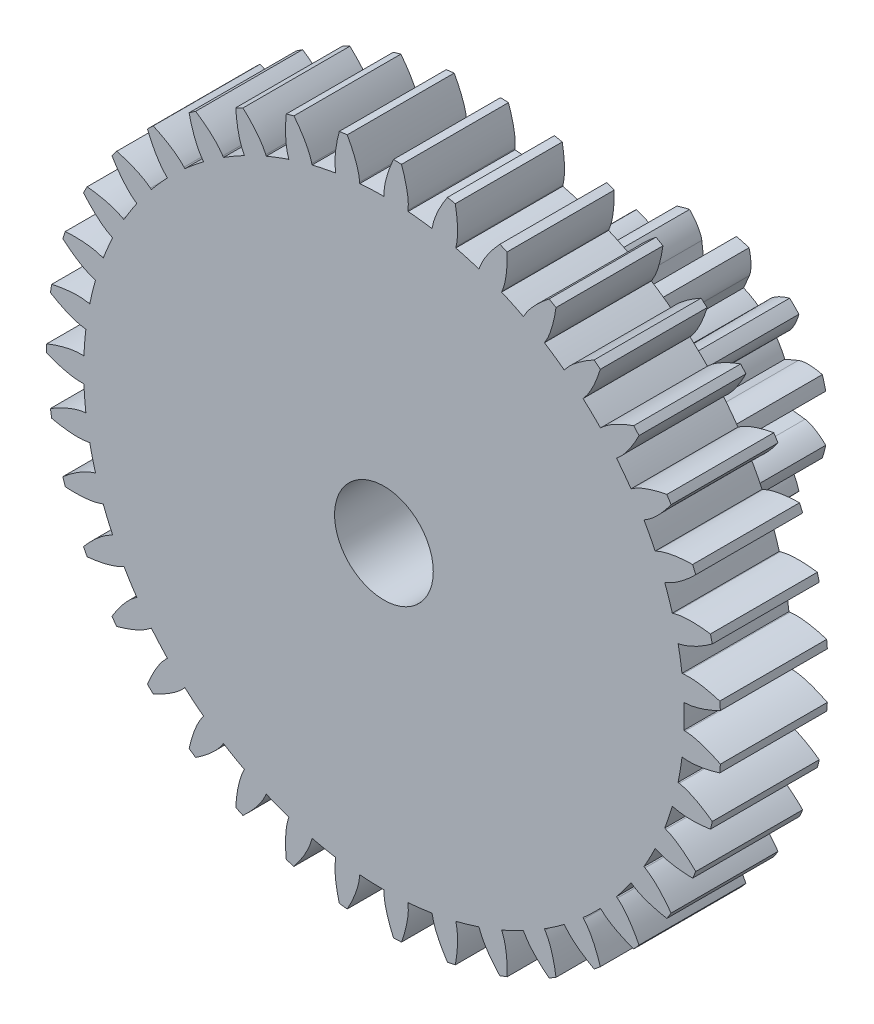
SolidWorks part; units mm, degrees
ref_plane "前视基准面" through (0, 0, 0) normal (0, 0, 1) x (1, 0, 0)
ref_plane "上视基准面" through (0, 0, 0) normal (0, 1, 0) x (1, 0, 0)
ref_plane "右视基准面" through (0, 0, 0) normal (1, 0, 0) x (0, 0, -1)
other "Configuration Table"
sketch "草图1" plane through (0, 0, 0) normal (0, 0, 1) x (1, 0, 0)
  line L0 (0, 0) -> (1.2, 0) construction
  line L1 (0, 0) -> (1.1897, 0.1566) construction
  line L2 (0, 0) -> (1.1195, 0.1354)
  line L3 (1.1897, 0.1566) -> (1.1897, -0.1566) construction
  line L4 (0, 0) -> (1.1195, -0.1354)
  circle A0 centre (0, 0) radius 1.4
  circle A1 centre (0, 0) radius 1.2 construction
  circle A2 centre (0, 0) radius 0.95
  circle A3 centre (0, 0) radius 1.1276 construction
  circle A4 centre (0, 0) radius 0.6
  spline S0 degree 4 poles (1.1195, 0.1354) (1.128, 0.1365) (1.1516, 0.1411) (1.1949, 0.157) (1.2609, 0.1921) (1.3385, 0.2504) (1.4265, 0.3386) (1.513, 0.4563) (1.5884, 0.5979) (1.6479, 0.7602) (1.6868, 0.9286) (1.7064, 1.1002) (1.7082, 1.2814) (1.6868, 1.5048) (1.6275, 1.7661) (1.5147, 2.0566) (1.3415, 2.356) (1.1264, 2.6272) (0.878, 2.867) (0.599, 3.0728) (0.3008, 3.2436) (-0.0211, 3.378) (-0.346, 3.4768) (-0.6967, 3.5387) (-0.9642, 3.5622) (-1.2659, 3.561) (-1.4376, 3.5485) (-1.6326, 3.5286) (-1.737, 3.508) (-1.8243, 3.4941) (-1.8493, 3.4877) (-1.868, 3.4841) knots 0 0 0 0 0 0.005604 0.015718 0.02996 0.048734 0.068727 0.096889 0.125051 0.153212 0.181374 0.209535 0.237696 0.271429 0.327752 0.384075 0.440398 0.496721 0.553044 0.609367 0.66569 0.722013 0.778336 0.834659 0.890982 0.909091 0.954545 0.977273 0.988636 1 1 1 1 1 construction
  spline S1 degree 4 poles (1.1195, 0.1354) (1.128, 0.1365) (1.1516, 0.1411) (1.1949, 0.157) (1.2609, 0.1921) (1.3385, 0.2504) (1.4265, 0.3386) (1.513, 0.4563) (1.5884, 0.5979) (1.6479, 0.7602) (1.6868, 0.9286) (1.7064, 1.1002) (1.7082, 1.2814) (1.6868, 1.5048) (1.6275, 1.7661) (1.5147, 2.0566) (1.3415, 2.356) (1.1264, 2.6272) (0.878, 2.867) (0.599, 3.0728) (0.3008, 3.2436) (-0.0211, 3.378) (-0.346, 3.4768) (-0.6967, 3.5387) (-0.9642, 3.5622) (-1.1881, 3.5613) (-1.292, 3.5571) (-1.3172, 3.5557) knots 0 0 0 0 0 0.005604 0.015718 0.02996 0.048734 0.068727 0.096889 0.125051 0.153212 0.181374 0.209535 0.237696 0.271429 0.327752 0.384075 0.440398 0.496721 0.553044 0.609367 0.66569 0.722013 0.778336 0.834659 0.890982 0.909091 0.909091 0.909091 0.909091 0.909091
  spline S2 degree 4 poles (1.1195, -0.1354) (1.128, -0.1365) (1.1516, -0.1411) (1.1949, -0.157) (1.2609, -0.1921) (1.3385, -0.2504) (1.4265, -0.3386) (1.513, -0.4563) (1.5884, -0.5979) (1.6479, -0.7602) (1.6868, -0.9286) (1.7064, -1.1002) (1.7082, -1.2814) (1.6868, -1.5048) (1.6275, -1.7661) (1.5147, -2.0566) (1.3415, -2.356) (1.1264, -2.6272) (0.878, -2.867) (0.599, -3.0728) (0.3008, -3.2436) (-0.0211, -3.378) (-0.346, -3.4768) (-0.6967, -3.5387) (-0.9642, -3.5622) (-1.2659, -3.561) (-1.4376, -3.5485) (-1.6326, -3.5286) (-1.737, -3.508) (-1.8243, -3.4941) (-1.8493, -3.4877) (-1.868, -3.4841) knots 0 0 0 0 0 0.005604 0.015718 0.02996 0.048734 0.068727 0.096889 0.125051 0.153212 0.181374 0.209535 0.237696 0.271429 0.327752 0.384075 0.440398 0.496721 0.553044 0.609367 0.66569 0.722013 0.778336 0.834659 0.890982 0.909091 0.954545 0.977273 0.988636 1 1 1 1 1 construction
  spline S3 degree 4 poles (1.1195, -0.1354) (1.128, -0.1365) (1.1516, -0.1411) (1.1949, -0.157) (1.2609, -0.1921) (1.3385, -0.2504) (1.4265, -0.3386) (1.513, -0.4563) (1.5884, -0.5979) (1.6479, -0.7602) (1.6868, -0.9286) (1.7064, -1.1002) (1.7082, -1.2814) (1.6868, -1.5048) (1.6275, -1.7661) (1.5147, -2.0566) (1.3415, -2.356) (1.1264, -2.6272) (0.878, -2.867) (0.599, -3.0728) (0.3008, -3.2436) (-0.0211, -3.378) (-0.346, -3.4768) (-0.6967, -3.5387) (-0.9642, -3.5622) (-1.1881, -3.5613) (-1.292, -3.5571) (-1.3172, -3.5557) knots 0 0 0 0 0 0.005604 0.015718 0.02996 0.048734 0.068727 0.096889 0.125051 0.153212 0.181374 0.209535 0.237696 0.271429 0.327752 0.384075 0.440398 0.496721 0.553044 0.609367 0.66569 0.722013 0.778336 0.834659 0.890982 0.909091 0.909091 0.909091 0.909091 0.909091
  point P15 (1.1897, 0)
  dimension "齿顶圆直径" = 2.8
  dimension "分度圆直径" = 2.4
  dimension "齿根圆直径" = 1.9
  dimension "基圆直径" = 2.2553
  dimension "内孔直径" = 1.2
  dimension "渐近线镜像线夹角" = 7.5
extrude "凸台-拉伸1" add sketch "草图1" along normal blind 2.7 contours A0 | A4
extrude "切除-拉伸1" cut sketch "草图1<3>" along normal through all contours A2 S3 A0 S1 region at (1.2063, 0, 0)
sketch "草图1<3>" plane through (0, 0, 0) normal (0, 0, 1) x (1, 0, 0) same geometry as "草图1"
pattern_circular "阵列(圆周)1" count 12 every 30 about axis through (0, 0, 2.7) along (0, 0, 1) of "切除-拉伸1"
sketch "草图2" plane through (0, 0, 2.7) normal (0, 0, 1) x (1, 0, 0)
  line L0 (0, 0) -> (3.9, 0) construction
  line L1 (0, 0) -> (3.6618, 0.1476)
  line L2 (0, 0) -> (3.6618, -0.1476)
  line L3 (3.6618, 0.1476) -> (3.6618, -0.1476) construction
  circle A0 centre (0, 0) radius 3.9 construction
  circle A1 centre (0, 0) radius 3.6648 construction
  circle A2 centre (0, 0) radius 3.65
  circle A3 centre (0, 0) radius 4.1
  circle A4 centre (0, 0) radius 0.6
  spline S0 degree 4 poles (3.6618, -0.1476) (3.6897, -0.1487) (3.7674, -0.1576) (3.9119, -0.1977) (4.1348, -0.2942) (4.4013, -0.463) (4.7093, -0.7258) (5.0201, -1.0848) (5.3014, -1.5238) (5.5949, -2.1619) (5.7801, -2.8411) (5.869, -3.5665) (5.856, -4.4361) (5.7315, -5.2982) (5.4421, -6.2685) (4.9581, -7.2836) (4.3333, -8.2181) (3.5885, -9.0594) (2.7425, -9.7986) (1.8136, -10.4296) (0.8175, -10.9486) (-0.098, -11.3031) (-0.9077, -11.5355) (-1.5224, -11.6672) (-1.9404, -11.7375) (-2.2806, -11.7841) (-2.573, -11.8149) (-2.8026, -11.8357) (-3.064, -11.8509) (-3.329, -11.8626) (-3.5941, -11.8675) (-4.06, -11.8656) (-4.4391, -11.8411) (-4.8329, -11.8129) (-5.0231, -11.7865) (-5.1504, -11.7728) knots 0 0 0 0 0 0.005604 0.015718 0.02996 0.048734 0.068727 0.096889 0.125051 0.153212 0.209535 0.237696 0.271429 0.327752 0.384075 0.440398 0.496721 0.553044 0.609367 0.66569 0.722013 0.778336 0.806497 0.834659 0.84874 0.86282 0.876901 0.890982 0.900036 0.909091 0.931818 0.954545 0.977273 1 1 1 1 1 construction
  spline S1 degree 4 poles (3.6618, -0.1476) (3.6897, -0.1487) (3.7674, -0.1576) (3.9119, -0.1977) (4.1348, -0.2942) (4.4013, -0.463) (4.7093, -0.7258) (5.0201, -1.0848) (5.3014, -1.5238) (5.5949, -2.1619) (5.7801, -2.8411) (5.869, -3.5665) (5.856, -4.4361) (5.7315, -5.2982) (5.4421, -6.2685) (4.9581, -7.2836) (4.3333, -8.2181) (3.5885, -9.0594) (2.7425, -9.7986) (1.8136, -10.4296) (0.8175, -10.9486) (-0.098, -11.3031) (-0.9077, -11.5355) (-1.5224, -11.6672) (-1.9404, -11.7375) (-2.2806, -11.7841) (-2.573, -11.8149) (-2.8026, -11.8357) (-3.064, -11.8509) (-3.2193, -11.8578) (-3.3015, -11.8605) (-3.3424, -11.8617) knots 0 0 0 0 0 0.005604 0.015718 0.02996 0.048734 0.068727 0.096889 0.125051 0.153212 0.209535 0.237696 0.271429 0.327752 0.384075 0.440398 0.496721 0.553044 0.609367 0.66569 0.722013 0.778336 0.806497 0.834659 0.84874 0.86282 0.876901 0.890982 0.900036 0.909091 0.909091 0.909091 0.909091 0.909091
  spline S2 degree 4 poles (3.6618, 0.1476) (3.6897, 0.1487) (3.7674, 0.1576) (3.9119, 0.1977) (4.1348, 0.2942) (4.4013, 0.463) (4.7093, 0.7258) (5.0201, 1.0848) (5.3014, 1.5238) (5.5949, 2.1619) (5.7801, 2.8411) (5.869, 3.5665) (5.856, 4.4361) (5.7315, 5.2982) (5.4421, 6.2685) (4.9581, 7.2836) (4.3333, 8.2181) (3.5885, 9.0594) (2.7425, 9.7986) (1.8136, 10.4296) (0.8175, 10.9486) (-0.098, 11.3031) (-0.9077, 11.5355) (-1.5224, 11.6672) (-1.9404, 11.7375) (-2.2806, 11.7841) (-2.573, 11.8149) (-2.8026, 11.8357) (-3.064, 11.8509) (-3.329, 11.8626) (-3.5941, 11.8675) (-4.06, 11.8656) (-4.4391, 11.8411) (-4.8329, 11.8129) (-5.0231, 11.7865) (-5.1504, 11.7728) knots 0 0 0 0 0 0.005604 0.015718 0.02996 0.048734 0.068727 0.096889 0.125051 0.153212 0.209535 0.237696 0.271429 0.327752 0.384075 0.440398 0.496721 0.553044 0.609367 0.66569 0.722013 0.778336 0.806497 0.834659 0.84874 0.86282 0.876901 0.890982 0.900036 0.909091 0.931818 0.954545 0.977273 1 1 1 1 1 construction
  spline S3 degree 4 poles (3.6618, 0.1476) (3.6897, 0.1487) (3.7674, 0.1576) (3.9119, 0.1977) (4.1348, 0.2942) (4.4013, 0.463) (4.7093, 0.7258) (5.0201, 1.0848) (5.3014, 1.5238) (5.5949, 2.1619) (5.7801, 2.8411) (5.869, 3.5665) (5.856, 4.4361) (5.7315, 5.2982) (5.4421, 6.2685) (4.9581, 7.2836) (4.3333, 8.2181) (3.5885, 9.0594) (2.7425, 9.7986) (1.8136, 10.4296) (0.8175, 10.9486) (-0.098, 11.3031) (-0.9077, 11.5355) (-1.5224, 11.6672) (-1.9404, 11.7375) (-2.2806, 11.7841) (-2.573, 11.8149) (-2.8026, 11.8357) (-3.064, 11.8509) (-3.2193, 11.8578) (-3.3015, 11.8605) (-3.3424, 11.8617) knots 0 0 0 0 0 0.005604 0.015718 0.02996 0.048734 0.068727 0.096889 0.125051 0.153212 0.209535 0.237696 0.271429 0.327752 0.384075 0.440398 0.496721 0.553044 0.609367 0.66569 0.722013 0.778336 0.806497 0.834659 0.84874 0.86282 0.876901 0.890982 0.900036 0.909091 0.909091 0.909091 0.909091 0.909091
  point P16 (3.6618, 0)
  dimension "内孔直径" = 1.2
  dimension "分度圆直径" = 7.8
  dimension "齿顶圆直径" = 8.2
  dimension "基圆直径" = 7.3296
  dimension "齿根圆直径" = 7.3
  dimension "渐开线镜像线夹角" = 2.308
extrude "凸台-拉伸2" add sketch "草图2" along normal blind 1.3 contours A3 | A4
extrude "切除-拉伸3" cut sketch "草图2<3>" along normal through all contours S3 L1 A2 L2 S1 A3 region at (3.8995, 0, 2.7)
sketch "草图2<3>" plane through (0, 0, 2.7) normal (0, 0, 1) x (1, 0, 0) same geometry as "草图2"
pattern_circular "阵列(圆周)2" count 39 over 360 about axis through (0, 0, 4) along (0, 0, 1) of "切除-拉伸3"
equation "\"m\"= 0.2'模数"
equation "\"z\"= 12'齿数"
equation "\"a\"= 20度'压力角"
equation "\"d\"= \"m\" * \"z\"'分度圆直径"
equation "\"da\"= ( \"z\" + 2 ) * \"m\"'齿顶圆直径"
equation "\"df\"= ( \"z\" - 2.5 ) * \"m\"'齿根圆直径"
equation "\"s\"= 0.5 * PI * \"m\"'分度圆齿厚"
equation "\"r\"= 0.38 * \"m\"'齿根圆角"
equation "\"B\"= 0.3 * \"d\"'齿厚"
equation "\"db\"= \"m\" * \"z\" * cos ( \"a\" )'基圆直径"
equation "\"rb\"= \"db\" / 2'基圆半径"
equation "\"齿顶圆直径@草图1\"= \"da\""
equation "\"分度圆直径@草图1\"= \"d\""
equation "\"齿根圆直径@草图1\"= \"df\""
equation "\"基圆直径@草图1\"= \"db\""
equation "\"渐近线镜像线夹角@草图1\"= 360 / 4 / \"z\""
equation "\"h\"= 2.7mm'齿轮厚度"
equation "\"ir\"= 1.2mm'内孔直径"
equation "\"内孔直径@草图1\"= \"ir\""
equation "\"齿轮厚@凸台-拉伸1\"= \"h\""
equation "\"齿轮夹角@阵列(圆周)1\"= 360 / \"z\""
equation "\"齿数@阵列(圆周)1\"= \"z\""
equation "\"m1\"= 0.2'模数"
equation "\"z1\"= 39'齿数"
equation "\"a1\"= 20度'压力角"
equation "\"d1\"= \"m1\" * \"z1\"'分度圆直径"
equation "\"da1\"= ( \"z1\" + 2 ) * \"m1\"'齿顶圆直径"
equation "\"df1\"= ( \"z1\" - 2.5 ) * \"m1\"'齿根圆直径"
equation "\"s1\"= 0.5 * PI * \"m1\"'分度圆齿厚"
equation "\"r1\"= 0.38 * \"m1\"'齿根圆角"
equation "\"B1\"= 0.3 * \"d1\"'齿厚"
equation "\"db1\"= \"m1\" * \"z1\" * cos ( \"a1\" )'基圆直径"
equation "\"rb1\"= \"db1\" / 2'基圆半径"
equation "\"分度圆直径@草图2\"= \"d1\""
equation "\"齿顶圆直径@草图2\"= \"da1\""
equation "\"基圆直径@草图2\"= \"db1\""
equation "\"齿根圆直径@草图2\"= \"df1\""
equation "\"渐开线镜像线夹角@草图2\"= 360 / 4 / \"z1\""
equation "\"内孔直径@草图2\"= \"ir\""
equation "\"二层齿轮厚@凸台-拉伸2\" = \"h1\""
equation "\"h1\"= 1.3'齿轮厚度"
equation "\"二层齿数@阵列(圆周)2\"= \"z1\""
